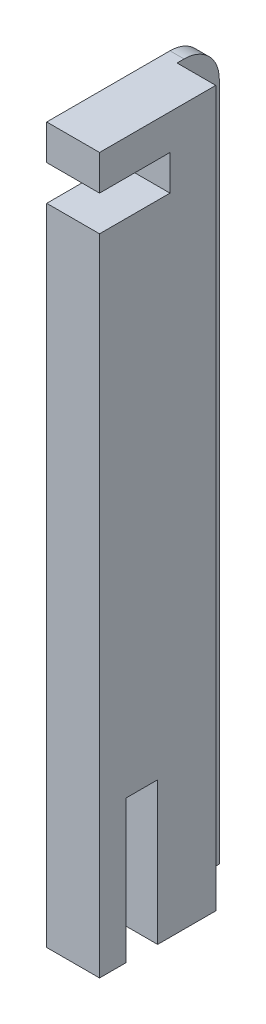
SolidWorks part; units mm, degrees
ref_plane "정면" through (0, 0, 0) normal (0, 0, 1) x (1, 0, 0)
ref_plane "윗면" through (0, 0, 0) normal (0, 1, 0) x (1, 0, 0)
ref_plane "우측면" through (0, 0, 0) normal (1, 0, 0) x (0, 0, -1)
sketch "스케치1" plane through (0, 0, 0) normal (0, 0, 1) x (1, 0, 0)
  line L0 (-318.5049, 0) -> (318.5049, 0) construction
  line L1 (0, 0) -> (0, -258.8265) construction
  line L2 (-168, 0) -> (168, 0)
  line L3 (-168, -20) -> (168, -20)
  line L4 (168, -20) -> (168, 0) construction
  line L5 (168, -20) -> (168, -340)
  line L6 (172, -340) -> (172, 0)
  line L7 (168, 0) -> (183, 0)
  line L8 (183, 0) -> (183, -340)
  line L9 (183, -340) -> (168, -340)
  line L10 (-168, -20) -> (-168, 0) construction
  line L11 (-183, -340) -> (-168, -340)
  line L12 (-183, 0) -> (-183, -340)
  line L13 (-168, 0) -> (-183, 0)
  line L14 (-172, -340) -> (-172, 0)
  line L15 (-168, -20) -> (-168, -340)
  line L16 (168, -20) -> (168, 0)
  line L17 (-168, -20) -> (-168, 0)
  point P14 (0, -20)
  dimension "D1" = 168
  dimension "D2" = 20
  dimension "D3" = 4
  dimension "D4" = 340
  dimension "D5" = 15
extrude "보스-돌출1" add sketch "스케치1" along normal blind 26 contours L3 L5 L9 L8 L7 L2 L13 L12 L11 L15
extrude "보스-돌출2" add sketch "스케치1<4>" against normal blind 19 contours L16 L5 L9 L6 L7 | L15 L17 L13 L14 L11 region at (-170, -170, 0) region at (170, -170, 0)
sketch "스케치1<4>" plane through (0, 0, 0) normal (0, 0, 1) x (1, 0, 0) same geometry as "스케치1"
fillet "필렛1" radius 10 4 edges at (-170, 0, -19) (170, 0, -19) (170, -340, -19) (-170, -340, -19)
sketch "스케치2" plane through (172, 0, 0) normal (1, 0, 0) x (0, 0, -1)
  line L0 (14, -340) -> (14, 0)
  line L1 (12, 0) -> (12, -340)
  line L4 (19, -330) -> (19, -10)
  line L5 (9, 0) -> (0, 0)
  line L6 (0, 0) -> (0, -340)
  line L7 (0, -340) -> (9, -340)
  line L8 (19, -330) -> (19, -10)
  line L9 (9, 0) -> (0, 0)
  line L10 (0, 0) -> (0, -340)
  line L11 (0, -340) -> (9, -340)
  arc A2 (19, -10) -> (9, 0) centre (9, -10) ccw
  arc A3 (9, -340) -> (19, -330) centre (9, -330) ccw
  arc A4 (19, -10) -> (9, 0) centre (9, -10) ccw
  arc A5 (9, -340) -> (19, -330) centre (9, -330) ccw
  dimension "D2" = 5
  dimension "D3" = 2
  dimension "D1" = 0
sketch "스케치3" plane through (168, 0, 0) normal (-1, 0, 0) x (0, 0, 1)
  line L0 (-12, 0) -> (-12, -340) construction
  line L1 (-14, -340) -> (-14, 0) construction
  line L2 (-12, 0) -> (-12, -340)
  line L3 (-14, -340) -> (-14, 0)
  line L4 (-19, -10) -> (-19, -330)
  line L5 (0, 0) -> (-9, 0)
  line L6 (0, -340) -> (0, 0)
  line L7 (-9, -340) -> (0, -340)
  line L8 (-19, -10) -> (-19, -330)
  line L9 (0, 0) -> (-9, 0)
  line L10 (0, -340) -> (0, 0)
  line L11 (-9, -340) -> (0, -340)
  arc A2 (-9, 0) -> (-19, -10) centre (-9, -10) ccw
  arc A3 (-19, -330) -> (-9, -340) centre (-9, -330) ccw
  arc A4 (-9, 0) -> (-19, -10) centre (-9, -10) ccw
  arc A5 (-19, -330) -> (-9, -340) centre (-9, -330) ccw
  dimension "D1" = 0
sketch "스케치5" plane through (0, 0, 0) normal (0, 1, 0) x (1, 0, 0)
  line L0 (-7, 0) -> (-7, -26)
  line L1 (7, 0) -> (7, -26)
  line L2 (-168, 0) -> (-168, -6)
  line L3 (-168, -6) -> (-7, -6)
  line L4 (7, -6) -> (168, -6)
  line L5 (168, -6) -> (168, 0)
  line L12 (-168, 0) -> (-168, 9)
  line L13 (-168, 9) -> (-172, 9)
  line L14 (-172, 9) -> (-172, 0)
  line L15 (-172, 0) -> (-183, 0)
  line L16 (-183, 0) -> (-183, -26)
  line L17 (-183, -26) -> (183, -26)
  line L18 (183, -26) -> (183, 0)
  line L19 (183, 0) -> (172, 0)
  line L20 (172, 0) -> (172, 9)
  line L21 (172, 9) -> (168, 9)
  line L22 (168, 9) -> (168, 0)
  line L23 (168, 0) -> (-168, 0)
  line L24 (-168, 0) -> (-168, 9)
  line L25 (-168, 9) -> (-172, 9)
  line L26 (-172, 9) -> (-172, 0)
  line L27 (-172, 0) -> (-183, 0)
  line L28 (-183, 0) -> (-183, -26)
  line L29 (-183, -26) -> (183, -26)
  line L30 (183, -26) -> (183, 0)
  line L31 (183, 0) -> (172, 0)
  line L32 (172, 0) -> (172, 9)
  line L33 (172, 9) -> (168, 9)
  line L34 (168, 9) -> (168, 0)
  line L35 (168, 0) -> (-168, 0)
  line M27 (168, 0) -> (-168, 0)
  dimension "D2" = 7
  dimension "D3" = 7
  dimension "D4" = 6
  dimension "D1" = 0
extrude "컷-돌출1" cut sketch "스케치5" against normal blind 52 contours L2 L3 L0 M27 | L4 L5 L1 M27 region at (-87.5, 0, 3) region at (87.5, 0, 3)
extrude "보스-돌출4" add sketch "스케치1<5>" against normal blind 7 contours L9 L8 L7 L6 | L11 L14 L13 L12 region at (-177.5, -170, 0) region at (177.5, -170, 0)
sketch "스케치1<5>" plane through (0, 0, 0) normal (0, 0, 1) x (1, 0, 0) same geometry as "스케치1"
sketch "스케치6" plane through (0, -340, 0) normal (0, -1, 0) x (1, 0, 0)
  line L0 (-172, -7) -> (-126.7636, -7) construction
  line L1 (-172, -7) -> (-168, -7)
  line L2 (-168, -7) -> (-168, -5)
  line L3 (-168, -5) -> (-174.5, -5)
  line L4 (-174.5, -5) -> (-174.5, -7)
  line L5 (-181.1, -7) -> (-181.1, -5)
  line L6 (-172, -7) -> (-172, -9)
  line L7 (-172, -9) -> (-168, -9)
  line L8 (-168, -9) -> (-168, 26)
  line L9 (-168, 26) -> (-183, 26)
  line L10 (-183, 26) -> (-183, -7)
  line L11 (-183, -7) -> (-172, -7)
  line L12 (-172, -7) -> (-172, -9)
  line L13 (-172, -9) -> (-168, -9)
  line L14 (-168, -9) -> (-168, 26)
  line L15 (-168, 26) -> (-183, 26)
  line L16 (-183, 26) -> (-183, -7)
  line L17 (-183, -7) -> (-172, -7)
  line L18 (-181.1, -5) -> (-183, -5)
  line L19 (-181.1, -5) -> (-174.5, -5)
  line L20 (-168, 26) -> (-168, 36)
  line L21 (-168, 36) -> (-183, 36)
  line L22 (-183, 36) -> (-183, 26)
  line L23 (-168, 36) -> (-168, 45)
  line L24 (-168, 45) -> (-183, 45)
  line L25 (-183, 45) -> (-183, 36)
  line M14 (-168, -9) -> (-168, 26)
  line M15 (-168, 26) -> (-183, 26)
  line M17 (-183, -7) -> (-172, -7)
  dimension "D2" = 6.5
  dimension "D3" = 2
  dimension "D4" = 6.6
  dimension "D5" = 41
  dimension "D6" = 9
  dimension "D1" = 0
extrude "보스-돌출5" add sketch "스케치6" along normal blind 28 contours L5 L18 L16 M17 | L19 L5 L4 M17 | L3 L4 L1 M17 M14 region at (-171.25, -340, -6) region at (-177.8, -340, -6) region at (-182.05, -340, -6)
extrude "컷-돌출2" cut sketch "스케치6<3>" along normal blind 5 contours L19 L5 L4 M17 region at (-177.8, -340, -6)
sketch "스케치6<3>" plane through (0, -340, 0) normal (0, -1, 0) x (1, 0, 0) same geometry as "스케치6"
fillet "필렛2" radius 20 1 edges at (-170, -340, -7)
extrude "보스-돌출6" add sketch "스케치6<4>" against normal blind 30 contours L21 L22 L20 M15 | L24 L25 L21 L23 region at (-175.5, -340, 31) region at (-175.5, -340, 40.5)
sketch "스케치6<4>" plane through (0, -340, 0) normal (0, -1, 0) x (1, 0, 0) same geometry as "스케치6"
extrude "보스-돌출7" add sketch "스케치6<5>" along normal blind 28 contours L24 L25 L21 L23 region at (-175.5, -340, 40.5)
sketch "스케치6<5>" plane through (0, -340, 0) normal (0, -1, 0) x (1, 0, 0) same geometry as "스케치6"
sketch "스케치9" plane through (-183, 0, 0) normal (-1, 0, 0) x (0, 0, 1)
  line L0 (45, -310) -> (26, -270)
  line L1 (26, 0) -> (26, -310) construction
  line L12 (26, 0) -> (-7, 0)
  line L13 (-7, 0) -> (-7, -368)
  line L14 (-7, -368) -> (-5, -368)
  line L15 (-5, -368) -> (-5, -340)
  line L16 (-5, -340) -> (36, -340)
  line L17 (36, -340) -> (36, -368)
  line L18 (36, -368) -> (45, -368)
  line L19 (45, -368) -> (45, -310)
  line L20 (45, -310) -> (26, -310)
  line L21 (26, -310) -> (26, 0)
  line L22 (26, 0) -> (-7, 0)
  line L23 (-7, 0) -> (-7, -368)
  line L24 (-7, -368) -> (-5, -368)
  line L25 (-5, -368) -> (-5, -340)
  line L26 (-5, -340) -> (36, -340)
  line L27 (36, -340) -> (36, -368)
  line L28 (36, -368) -> (45, -368)
  line L29 (45, -368) -> (45, -310)
  line L30 (45, -310) -> (26, -310)
  line L31 (26, -310) -> (26, 0)
  line M19 (45, -310) -> (26, -310)
  line M20 (26, -310) -> (26, 0)
  dimension "D2" = 40
  dimension "D1" = 0
extrude "보스-돌출8" add sketch "스케치9" against normal blind 15 contours L0 M19 M20 region at (-183, -296.6667, 32.3333)
fillet "필렛3" radius 20 2 edges at (-175.5, -270, 26) (-175.5, -310, 45)
mirror "대칭 복사2" about plane through (0, 0, 0) normal (1, 0, 0) of "보스-돌출5", "컷-돌출2", "필렛3", "보스-돌출6", "보스-돌출7", "보스-돌출8"
fillet "필렛4" radius 20 1 edges at (170, -340, -7)
sketch "스케치10" plane through (183, 0, 0) normal (1, 0, 0) x (0, 0, -1)
  line L0 (-27.9344, -274.0725) -> (-43.0656, -305.9275) construction
  line L1 (-45, -314.5086) -> (-45, -368) construction
  line L2 (-45, -368) -> (-36, -368) construction
  line L3 (-36, -368) -> (-36, -340) construction
  line L4 (-36, -340) -> (5, -340) construction
  line L5 (5, -340) -> (5, -368) construction
  line L6 (5, -368) -> (7, -368) construction
  line L7 (7, -368) -> (7, -354) construction
  line L8 (19, -330) -> (19, -10) construction
  line L9 (9, 0) -> (-6, 0) construction
  line L10 (-6, 0) -> (-6, -20) construction
  line L11 (-6, -20) -> (-26, -20) construction
  line L12 (-26, -20) -> (-26, -265.4914) construction
  line L13 (-27.9344, -274.0725) -> (-43.0656, -305.9275) construction
  line L14 (-45, -314.5086) -> (-45, -368) construction
  line L15 (-45, -368) -> (-36, -368) construction
  line L16 (-36, -368) -> (-36, -340) construction
  line L17 (-36, -340) -> (5, -340) construction
  line L18 (5, -340) -> (5, -368) construction
  line L19 (5, -368) -> (7, -368) construction
  line L20 (7, -368) -> (7, 0) construction
  line L21 (7, 0) -> (-26, 0) construction
  line L22 (-26, 0) -> (-26, -265.4914) construction
  line L23 (-27.9344, -274.0725) -> (-43.0656, -305.9275)
  line L24 (-45, -314.5086) -> (-45, -368)
  line L25 (-45, -368) -> (-36, -368)
  line L26 (-36, -368) -> (-36, -340)
  line L27 (-36, -340) -> (5, -340)
  line L28 (5, -340) -> (5, -368)
  line L29 (5, -368) -> (7, -368)
  line L30 (7, -368) -> (7, -354)
  line L31 (19, -330) -> (19, -10)
  line L32 (9, 0) -> (-6, 0)
  line L33 (-6, 0) -> (-6, -20)
  line L34 (-6, -20) -> (-26, -20)
  line L35 (-26, -20) -> (-26, -265.4914)
  line L36 (-27.9344, -274.0725) -> (-43.0656, -305.9275)
  line L37 (-45, -314.5086) -> (-45, -368)
  line L38 (-45, -368) -> (-36, -368)
  line L39 (-36, -368) -> (-36, -340)
  line L40 (-36, -340) -> (5, -340)
  line L41 (5, -340) -> (5, -368)
  line L42 (5, -368) -> (7, -368)
  line L43 (7, -368) -> (7, 0)
  line L44 (7, 0) -> (-26, 0)
  line L45 (-26, 0) -> (-26, -265.4914)
  line L46 (-26, -10) -> (-6, -10)
  arc A0 (-43.0656, -305.9275) -> (-45, -314.5086) centre (-25, -314.5086) ccw construction
  arc A1 (15, -338) -> (7, -354) centre (27, -354) ccw construction
  arc A2 (15, -338) -> (19, -330) centre (9, -330) ccw construction
  arc A3 (19, -10) -> (9, 0) centre (9, -10) ccw construction
  arc A4 (-27.9344, -274.0725) -> (-26, -265.4914) centre (-46, -265.4914) ccw construction
  arc A5 (-43.0656, -305.9275) -> (-45, -314.5086) centre (-25, -314.5086) ccw construction
  arc A6 (-27.9344, -274.0725) -> (-26, -265.4914) centre (-46, -265.4914) ccw construction
  arc A7 (-43.0656, -305.9275) -> (-45, -314.5086) centre (-25, -314.5086) ccw
  arc A8 (15, -338) -> (7, -354) centre (27, -354) ccw
  arc A9 (15, -338) -> (19, -330) centre (9, -330) ccw
  arc A10 (19, -10) -> (9, 0) centre (9, -10) ccw
  arc A11 (-27.9344, -274.0725) -> (-26, -265.4914) centre (-46, -265.4914) ccw
  arc A12 (-43.0656, -305.9275) -> (-45, -314.5086) centre (-25, -314.5086) ccw
  arc A13 (-27.9344, -274.0725) -> (-26, -265.4914) centre (-46, -265.4914) ccw
sketch "스케치11" plane through (168, 0, 0) normal (-1, 0, 0) x (0, 0, 1)
  line L10 (43.0656, -305.9275) -> (27.9344, -274.0725)
  line L11 (45, -368) -> (45, -314.5086)
  line L12 (36, -368) -> (45, -368)
  line L13 (45, -368) -> (45, -314.5086)
  line L14 (43.0656, -305.9275) -> (27.9344, -274.0725)
  line L15 (26, -265.4914) -> (26, -20)
  line L16 (26, -20) -> (6, -20)
  line L17 (6, -20) -> (6, 0)
  line L18 (6, 0) -> (-9, 0)
  line L19 (-19, -10) -> (-19, -330)
  line L20 (-7, -354) -> (-7, -368)
  line L21 (-7, -368) -> (-5, -368)
  line L22 (-5, -368) -> (-5, -340)
  line L23 (-5, -340) -> (36, -340)
  line L24 (36, -340) -> (36, -368)
  line L25 (36, -368) -> (45, -368)
  line L26 (45, -368) -> (45, -314.5086)
  line L27 (43.0656, -305.9275) -> (27.9344, -274.0725)
  line L28 (26, -265.4914) -> (26, -20)
  line L29 (26, -20) -> (6, -20)
  line L30 (6, -20) -> (6, 0)
  line L31 (6, 0) -> (-9, 0)
  line L32 (-19, -10) -> (-19, -330)
  line L33 (-7, -354) -> (-7, -368)
  line L34 (-7, -368) -> (-5, -368)
  line L35 (-5, -368) -> (-5, -340)
  line L36 (-5, -340) -> (36, -340)
  line L37 (36, -340) -> (36, -368)
  line L38 (36, -368) -> (45, -368)
  line L39 (36, -340) -> (36, -368)
  line L40 (-5, -340) -> (36, -340)
  line L41 (-5, -368) -> (-5, -340)
  line L42 (-7, -368) -> (-5, -368)
  line L43 (-7, 0) -> (-7, -368)
  line L44 (26, 0) -> (-7, 0)
  line L45 (26, -265.4914) -> (26, 0)
  line L46 (43.0656, -305.9275) -> (27.9344, -274.0725)
  line L47 (45, -368) -> (45, -314.5086)
  line L48 (36, -368) -> (45, -368)
  line L49 (36, -340) -> (36, -368)
  line L50 (-5, -340) -> (36, -340)
  line L51 (-5, -368) -> (-5, -340)
  line L52 (-7, -368) -> (-5, -368)
  line L53 (-7, 0) -> (-7, -368)
  line L54 (26, 0) -> (-7, 0)
  line L55 (26, -265.4914) -> (26, 0)
  arc A2 (45, -314.5086) -> (43.0656, -305.9275) centre (25, -314.5086) ccw
  arc A3 (26, -265.4914) -> (27.9344, -274.0725) centre (46, -265.4914) ccw
  arc A4 (45, -314.5086) -> (43.0656, -305.9275) centre (25, -314.5086) ccw
  arc A5 (45, -314.5086) -> (43.0656, -305.9275) centre (25, -314.5086) ccw
  arc A6 (26, -265.4914) -> (27.9344, -274.0725) centre (46, -265.4914) ccw
  arc A7 (-9, 0) -> (-19, -10) centre (-9, -10) ccw
  arc A8 (-19, -330) -> (-15, -338) centre (-9, -330) ccw
  arc A9 (-7, -354) -> (-15, -338) centre (-27, -354) ccw
  arc A10 (45, -314.5086) -> (43.0656, -305.9275) centre (25, -314.5086) ccw
  arc A11 (26, -265.4914) -> (27.9344, -274.0725) centre (46, -265.4914) ccw
  arc A12 (-9, 0) -> (-19, -10) centre (-9, -10) ccw
  arc A13 (-19, -330) -> (-15, -338) centre (-9, -330) ccw
  arc A14 (-7, -354) -> (-15, -338) centre (-27, -354) ccw
  arc A15 (26, -265.4914) -> (27.9344, -274.0725) centre (46, -265.4914) ccw
  line M31 (45, -368) -> (45, -314.5086)
  arc M32 (45, -314.5086) -> (43.0656, -305.9275) centre (25, -314.5086) ccw
  line M33 (43.0656, -305.9275) -> (27.9344, -274.0725)
  arc M34 (27.9344, -274.0725) -> (26, -265.4914) centre (46, -265.4914) cw
  line M35 (26, -265.4914) -> (26, -20)
  line M36 (26, -20) -> (6, -20)
  line M37 (6, -20) -> (6, 0)
  line M38 (6, 0) -> (-9, 0)
  arc M39 (-9, 0) -> (-19, -10) centre (-9, -10) ccw
  line M40 (-19, -10) -> (-19, -330)
  arc M41 (-19, -330) -> (-15, -338) centre (-9, -330) ccw
  arc M42 (-15, -338) -> (-7, -354) centre (-27, -354) cw
  line M43 (-7, -354) -> (-7, -368)
  line M44 (-7, -368) -> (-5, -368)
  line M45 (-5, -368) -> (-5, -340)
  line M46 (-5, -340) -> (36, -340)
  line M47 (36, -340) -> (36, -368)
  line M48 (36, -368) -> (45, -368)
  dimension "D1" = 0
  dimension "D2" = 0
extrude "컷-돌출3" cut sketch "스케치11" along normal blind 617 contours L53 M38 M43 M44 M45 M46 M47 M48 M31 M32 M33 M34 M35 M36 M37 | L55 L54 M36 M37 | L53 L31 M39 M40 M41 M42 region at (168, -191.2863, 11.8028) region at (168, -10, 16) region at (168, -171.1237, -12.9334)
extrude "컷-돌출4" cut sketch "스케치10" against normal blind 617 contours L46 L45 L34 L33 region at (183, -15, 16)
sketch "스케치12" plane through (168, 0, 0) normal (-1, 0, 0) x (0, 0, 1)
  line L0 (18, -203) -> (18, -163)
  line L1 (18, -163) -> (10, -163)
  line L2 (10, -163) -> (10, -203)
  line L3 (10, -203) -> (-19, -203)
  line L4 (18.5, -203) -> (18.5, -162.5)
  line L5 (18.5, -162.5) -> (9.5, -162.5)
  line L6 (9.5, -162.5) -> (9.5, -203)
  line L15 (26, -183) -> (-19, -183) construction
  line L16 (26, -203) -> (18, -203)
  line L18 (-7, 0) -> (-9, 0)
  line L19 (-7, -354) -> (-7, 0)
  line L20 (-19, -10) -> (-19, -330)
  line L21 (-7, 0) -> (-9, 0)
  line L22 (-7, -354) -> (-7, 0)
  line L23 (-19, -10) -> (-19, -330)
  line L30 (6, -10) -> (26, -10)
  line L31 (26, -10) -> (26, 0)
  line L32 (26, 0) -> (-9, 0)
  line L33 (-19, -10) -> (-19, -330)
  line L34 (-7, -354) -> (-7, -368)
  line L35 (-7, -368) -> (-5, -368)
  line L36 (-5, -368) -> (-5, -340)
  line L37 (-5, -340) -> (36, -340)
  line L38 (36, -340) -> (36, -368)
  line L39 (36, -368) -> (45, -368)
  line L40 (45, -368) -> (45, -314.5086)
  line L41 (43.0656, -305.9275) -> (27.9344, -274.0725)
  line L42 (26, -265.4914) -> (26, -20)
  line L43 (26, -20) -> (6, -20)
  line L44 (6, -20) -> (6, -10)
  line L45 (6, -10) -> (26, -10)
  line L46 (26, -10) -> (26, 0)
  line L47 (26, 0) -> (-9, 0)
  line L48 (-19, -10) -> (-19, -330)
  line L49 (-7, -354) -> (-7, -368)
  line L50 (-7, -368) -> (-5, -368)
  line L51 (-5, -368) -> (-5, -340)
  line L52 (-5, -340) -> (36, -340)
  line L53 (36, -340) -> (36, -368)
  line L54 (36, -368) -> (45, -368)
  line L55 (45, -368) -> (45, -314.5086)
  line L56 (43.0656, -305.9275) -> (27.9344, -274.0725)
  line L57 (26, -265.4914) -> (26, -20)
  line L58 (26, -20) -> (6, -20)
  line L59 (6, -20) -> (6, -10)
  arc A8 (-7, -354) -> (-15, -338) centre (-27, -354) ccw
  arc A9 (-19, -330) -> (-15, -338) centre (-9, -330) ccw
  arc A10 (-9, 0) -> (-19, -10) centre (-9, -10) ccw
  arc A11 (-19, -330) -> (-15, -338) centre (-9, -330) ccw
  arc A12 (-7, -354) -> (-15, -338) centre (-27, -354) ccw
  arc A13 (45, -314.5086) -> (43.0656, -305.9275) centre (25, -314.5086) ccw
  arc A14 (26, -265.4914) -> (27.9344, -274.0725) centre (46, -265.4914) ccw
  arc A15 (-9, 0) -> (-19, -10) centre (-9, -10) ccw
  arc A16 (-19, -330) -> (-15, -338) centre (-9, -330) ccw
  arc A17 (-7, -354) -> (-15, -338) centre (-27, -354) ccw
  arc A18 (45, -314.5086) -> (43.0656, -305.9275) centre (25, -314.5086) ccw
  arc A19 (26, -265.4914) -> (27.9344, -274.0725) centre (46, -265.4914) ccw
  arc A20 (-9, 0) -> (-19, -10) centre (-9, -10) ccw
  arc A21 (-7, -354) -> (-15, -338) centre (-27, -354) ccw
  arc A22 (-19, -330) -> (-15, -338) centre (-9, -330) ccw
  arc A23 (-9, 0) -> (-19, -10) centre (-9, -10) ccw
  line M35 (-19, -10) -> (-19, -330)
  arc M36 (-19, -330) -> (-15, -338) centre (-9, -330) ccw
  arc M37 (-15, -338) -> (-7, -354) centre (-27, -354) cw
  line M38 (-7, -354) -> (-7, -368)
  line M39 (-7, -368) -> (-5, -368)
  line M40 (-5, -368) -> (-5, -340)
  line M41 (-5, -340) -> (36, -340)
  line M42 (36, -340) -> (36, -368)
  line M43 (36, -368) -> (45, -368)
  line M44 (45, -368) -> (45, -314.5086)
  arc M45 (45, -314.5086) -> (43.0656, -305.9275) centre (25, -314.5086) ccw
  line M46 (43.0656, -305.9275) -> (27.9344, -274.0725)
  arc M47 (27.9344, -274.0725) -> (26, -265.4914) centre (46, -265.4914) cw
  line M48 (26, -265.4914) -> (26, -20)
  dimension "D3" = 185
  dimension "D4" = 8
  dimension "D5" = 8
  dimension "D6" = 20
  dimension "D7" = 20
  dimension "D1" = 0
  dimension "D2" = 0
  dimension "D8" = 0.5
extrude "컷-돌출5" cut sketch "스케치12" against normal blind 37 contours L15 L0 L1 L2 | L0 L15 L2 L3 L22 L16 M38 M39 M40 M41 M42 M43 M44 M45 M46 M47 M48 | L15 L4 L5 L6 L2 L1 L0 | L4 L15 L0 L16 | L2 L15 L6 L3 | L22 L3 M37 M35 M36 region at (168, -280.3986, 14.7422) region at (168, -193, 18.25) region at (168, -173, 14) region at (168, -173, 18.2239) region at (168, -193, 9.75) region at (168, -271.7838, -12.8848)
